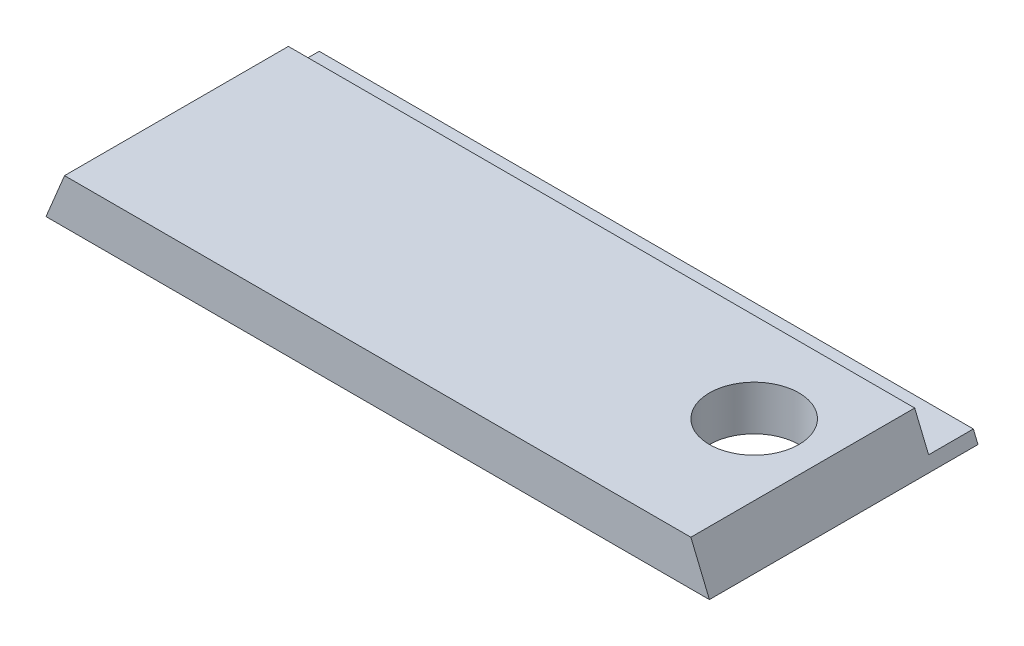
SolidWorks part; units mm, degrees
ref_plane "Front Plane" through (0, 0, 0) normal (0, 0, 1) x (1, 0, 0)
ref_plane "Top Plane" through (0, 0, 0) normal (0, 1, 0) x (1, 0, 0)
ref_plane "Right Plane" through (0, 0, 0) normal (1, 0, 0) x (0, 0, -1)
sketch "Sketch1" plane through (0, 0, 0) normal (0, 0, 1) x (1, 0, 0)
  line L0 (0, 0) -> (188.214, 0)
  line L1 (188.214, 0) -> (182.9535, 12.7)
  line L2 (182.9535, 12.7) -> (5.2605, 12.7)
  line L3 (5.2605, 12.7) -> (0, 0)
  dimension "D1" = 12.7
  dimension "D2" = 188.214
  dimension "D3" = 67.5
  dimension "D4" = 67.5
extrude "Boss-Extrude1" add sketch "Sketch1" along normal blind 76.2
sketch "Sketch2" plane through (0, 12.7, 0) normal (0, 1, 0) x (1, 0, 0)
  line L0 (188.214, -76.2) -> (188.214, 0) construction
  line L1 (188.214, -12.7) -> (0, -12.7)
  line L2 (188.214, -12.7) -> (188.214, 0)
  line L3 (188.214, 0) -> (0, 0)
  line L4 (0, -12.7) -> (0, 0)
  dimension "D1" = 12.7
extrude "Cut-Extrude1" cut sketch "Sketch2" against normal blind 9.525
sketch "Sketch3" plane through (0, 0, 0) normal (0, -1, 0) x (1, 0, 0)
  line L0 (0, 76.2) -> (188.214, 76.2) construction
  line L1 (188.214, 76.2) -> (188.214, 0) construction
  circle A0 centre (162.814, 38.1) radius 12.7
  dimension "D1" = 25.4
  dimension "D2" = 38.1
  dimension "D3" = 25.4
extrude "Cut-Extrude2" cut sketch "Sketch3" against normal through all
